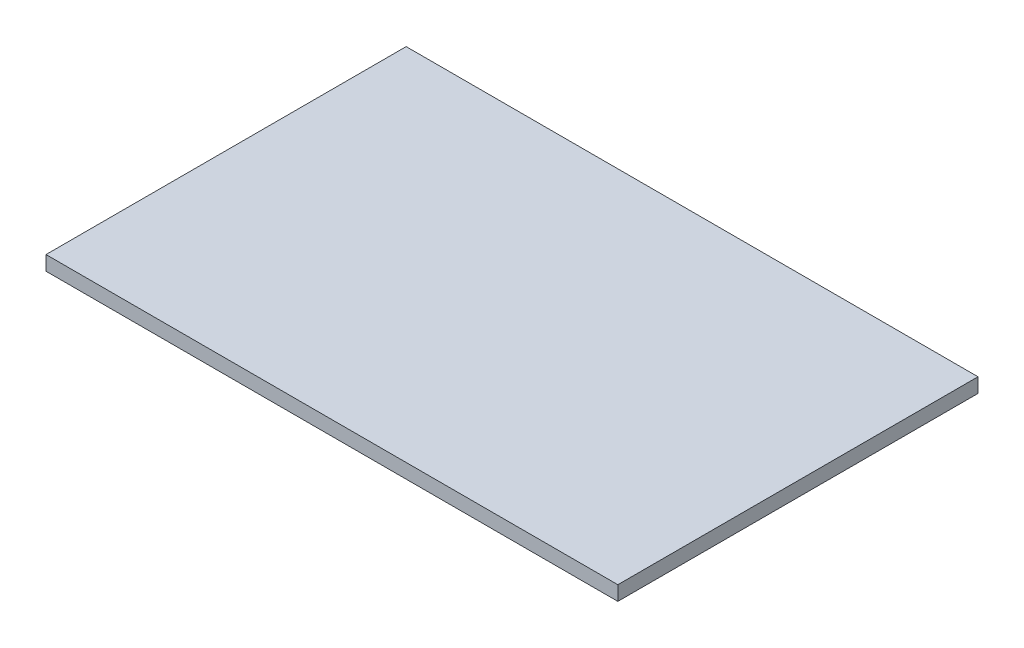
SolidWorks part; units mm, degrees
ref_plane "Front Plane" through (0, 0, 0) normal (0, 0, 1) x (1, 0, 0)
ref_plane "Top Plane" through (0, 0, 0) normal (0, 1, 0) x (1, 0, 0)
ref_plane "Right Plane" through (0, 0, 0) normal (1, 0, 0) x (0, 0, -1)
sketch "Sketch1" plane through (0, 0, 0) normal (0, 1, 0) x (1, 0, 0)
  line L1 (-583.0745, 466.4596) -> (918.9255, 466.4596)
  line L2 (-583.0745, 466.4596) -> (-583.0745, -479.5404)
  line L3 (-583.0745, -479.5404) -> (918.9255, -479.5404)
  line L4 (918.9255, 466.4596) -> (918.9255, -479.5404)
  line L5 (-533.0745, 416.4596) -> (868.9255, 416.4596)
  line L6 (-533.0745, 416.4596) -> (-533.0745, -429.5404)
  line L7 (-533.0745, -429.5404) -> (868.9255, -429.5404)
  line L8 (868.9255, 416.4596) -> (868.9255, -429.5404)
  dimension "D1" = 1502
  dimension "D2" = 946
  dimension "D3" = 50
  dimension "D4" = 50
  dimension "D5" = 50
  dimension "D6" = 50
extrude "Boss-Extrude1" add sketch "Sketch1" along normal blind 38 contours L1 L4 L3 L2
extrude "Cut-Extrude1" cut sketch "Sketch1<4>" along normal blind 30 contours L6 L7 L8 L5
sketch "Sketch1<4>" plane through (0, 0, 0) normal (0, 1, 0) x (1, 0, 0) same geometry as "Sketch1"
